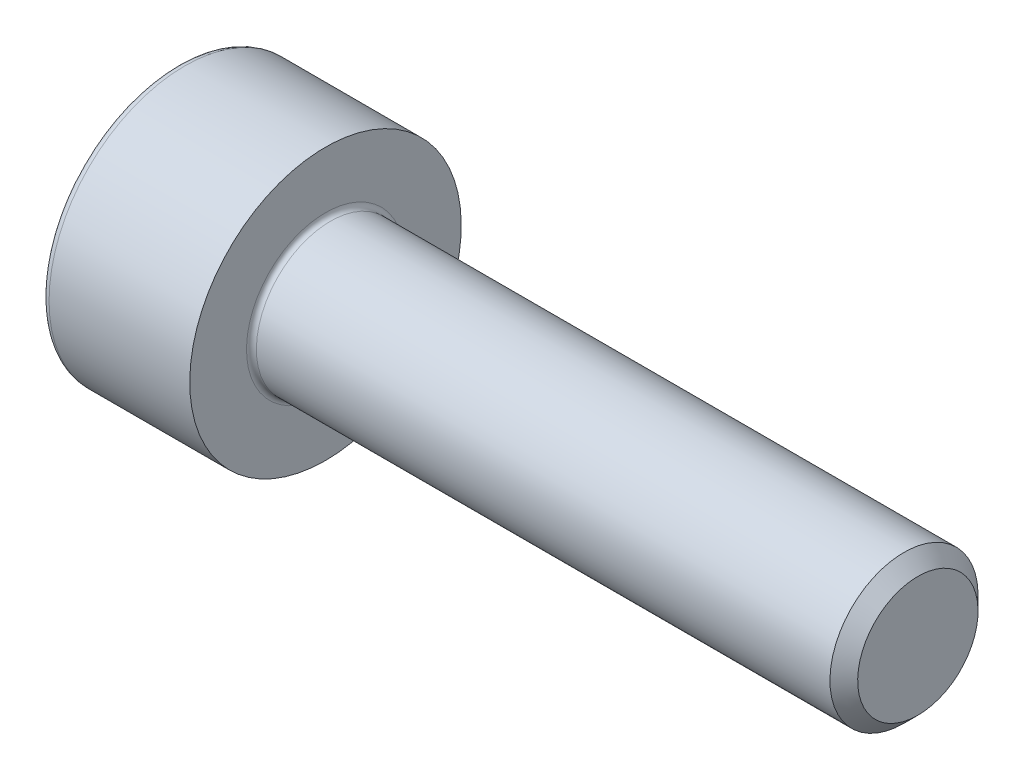
SolidWorks part; units mm, degrees
ref_plane "Front Plane" through (0, 0, 0) normal (0, 0, 1) x (1, 0, 0)
ref_plane "Top Plane" through (0, 0, 0) normal (0, 1, 0) x (1, 0, 0)
ref_plane "Right Plane" through (0, 0, 0) normal (1, 0, 0) x (0, 0, -1)
ref_axis "Axis_X" through (-1.88, 0, 0) along (1, 0, 0)
ref_axis "Axis_Y" through (0, 1.65, 0) along (0, -1, 0)
ref_axis "Axis_Z" through (0, 0, -1.65) along (0, 0, 1)
sketch "Sketch1" plane through (0, 0, 0) normal (0, 0, 1) x (1, 0, 0)
  line L0 (0, 0) -> (12, 0) construction
  line L1 (-3, 0) -> (-3, 2.75)
  line L2 (-3, 2.75) -> (0, 2.75)
  line L3 (0, 2.75) -> (0, 1.5)
  line L4 (0, 1.5) -> (12, 1.5)
  line L5 (12, 1.5) -> (12, 0)
  line L6 (12, 0) -> (-3, 0)
  dimension "MSM_51" = 5.5
  dimension "MSM_52" = 3
  dimension "MSM_53" = 12
  dimension "M" = 3
revolve "Revolve1" add sketch "Sketch1" angle 360 about L0
cosmetic thread "Thread1" parameters "ATD_1"=2.459
sketch "Sketch2" plane through (-3, 0, 0) normal (-1, 0, 0) x (0, 0, 1)
  line L1 (0, 1.478) -> (-1.28, 0.739)
  line L2 (-1.28, 0.739) -> (-1.28, -0.739)
  line L3 (-1.28, -0.739) -> (0, -1.478)
  line L4 (0, -1.478) -> (1.28, -0.739)
  line L5 (1.28, -0.739) -> (1.28, 0.739)
  line L6 (1.28, 0.739) -> (0, 1.478)
  circle A0 centre (0, 0) radius 1.28 construction
  dimension "MSM_55" = 2.56
extrude "Cut-Extrude1" cut sketch "Sketch2" against normal blind 1.3
fillet "Fillet1" radius 0.15 1 edges at (-3, -2.75, 0)
chamfer "Chamfer1" distance 0.281 angle 45 1 edges at (12, -1.5, 0)
fillet "Fillet2" radius 0.1 1 edges at (0, -1.5, 0)
equation "\"Factor\"= 1.082532"
